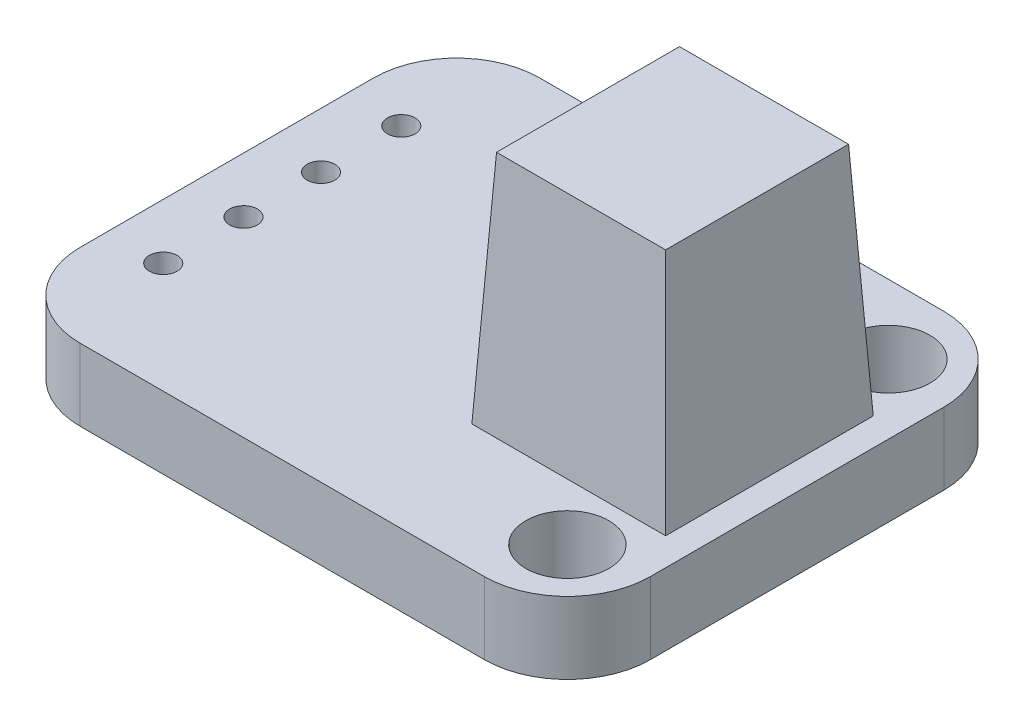
SolidWorks part; units mm, degrees
ref_plane "Front Plane" through (0, 0, 0) normal (0, 0, 1) x (1, 0, 0)
ref_plane "Top Plane" through (0, 0, 0) normal (0, 1, 0) x (1, 0, 0)
ref_plane "Right Plane" through (0, 0, 0) normal (1, 0, 0) x (0, 0, -1)
sketch "Sketch1" plane through (0, 0, 0) normal (0, 1, 0) x (1, 0, 0)
  line L1 (-10.3, -8.3) -> (10.3, -8.3)
  line L2 (-10.3, -8.3) -> (-10.3, 8.3)
  line L3 (-10.3, 8.3) -> (10.3, 8.3)
  line L4 (10.3, -8.3) -> (10.3, 8.3)
  line L5 (-10.3, -8.3) -> (10.3, 8.3) construction
  line L6 (-10.3, 8.3) -> (10.3, -8.3) construction
  point P0 (0, 0)
  dimension "D1" = 16.6
  dimension "D2" = 20.6
extrude "Boss-Extrude1" add sketch "Sketch1" along normal blind 2.6
fillet "Fillet1" radius 3 4 edges at (-10.3, 1.3, -8.3) (-10.3, 1.3, 8.3) (10.3, 1.3, -8.3) (10.3, 1.3, 8.3)
sketch "Sketch2" plane through (0, 2.6, 0) normal (0, 1, 0) x (1, 0, 0)
  line L0 (7.3, 8.3) -> (-7.3, 8.3) construction
  line L1 (10.3, -5.3) -> (10.3, 5.3) construction
  line L2 (-7.3, -8.3) -> (7.3, -8.3) construction
  circle A0 centre (7.8, 5.8) radius 1.5
  circle A1 centre (7.8, -5.8) radius 1.5
  point P4 (0, 0)
  dimension "D1" = 3
  dimension "D2" = 3
  dimension "D3" = 2.5
  dimension "D4" = 2.5
  dimension "D5" = 2.5
extrude "Cut-Extrude1" cut sketch "Sketch2" against normal blind 2.6
sketch "Sketch3" plane through (0, 2.6, 0) normal (0, 1, 0) x (1, 0, 0)
  line L1 (2.3, 3.75) -> (9.3, 3.75)
  line L2 (2.3, 3.75) -> (2.3, -3.75)
  line L3 (2.3, -3.75) -> (9.3, -3.75)
  line L4 (9.3, 3.75) -> (9.3, -3.75)
  line L5 (2.3, 3.75) -> (9.3, -3.75) construction
  line L6 (2.3, -3.75) -> (9.3, 3.75) construction
  line L8 (10.3, -5.3) -> (10.3, 5.3) construction
  point P0 (5.8, 0)
  point P5 (0, 0)
  point P7 (0, 0)
  point P10 (0, 0)
  dimension "D1" = 7.5
  dimension "D2" = 7
  dimension "D3" = 1
extrude "Boss-Extrude2" add sketch "Sketch3" along normal blind 8.5 draft 3
sketch "Sketch4" plane through (0, 2.6, 0) normal (0, 1, 0) x (1, 0, 0)
  line L0 (7.3, 8.3) -> (-7.3, 8.3) construction
  line L1 (-7.3, -8.3) -> (7.3, -8.3) construction
  line L3 (-10.3, 5.3) -> (-10.3, -5.3) construction
  circle A0 centre (-8.3, 4.3) radius 0.5
  circle A3 centre (-8.3, -4.3) radius 0.5
  circle A4 centre (-8.3, -1.4) radius 0.5
  circle A5 centre (-8.3, 1.4) radius 0.5
  point P15 (0, 0)
  point P16 (0, 0)
  point P17 (0, 0)
  dimension "D3" = 1
  dimension "D4" = 1
  dimension "D7" = 1
  dimension "D8" = 1
  dimension "D1" = 4
  dimension "D2" = 4
  dimension "D5" = 2.9
  dimension "D6" = 2.9
  dimension "D9" = 2
extrude "Cut-Extrude2" cut sketch "Sketch4" against normal blind 8.5
